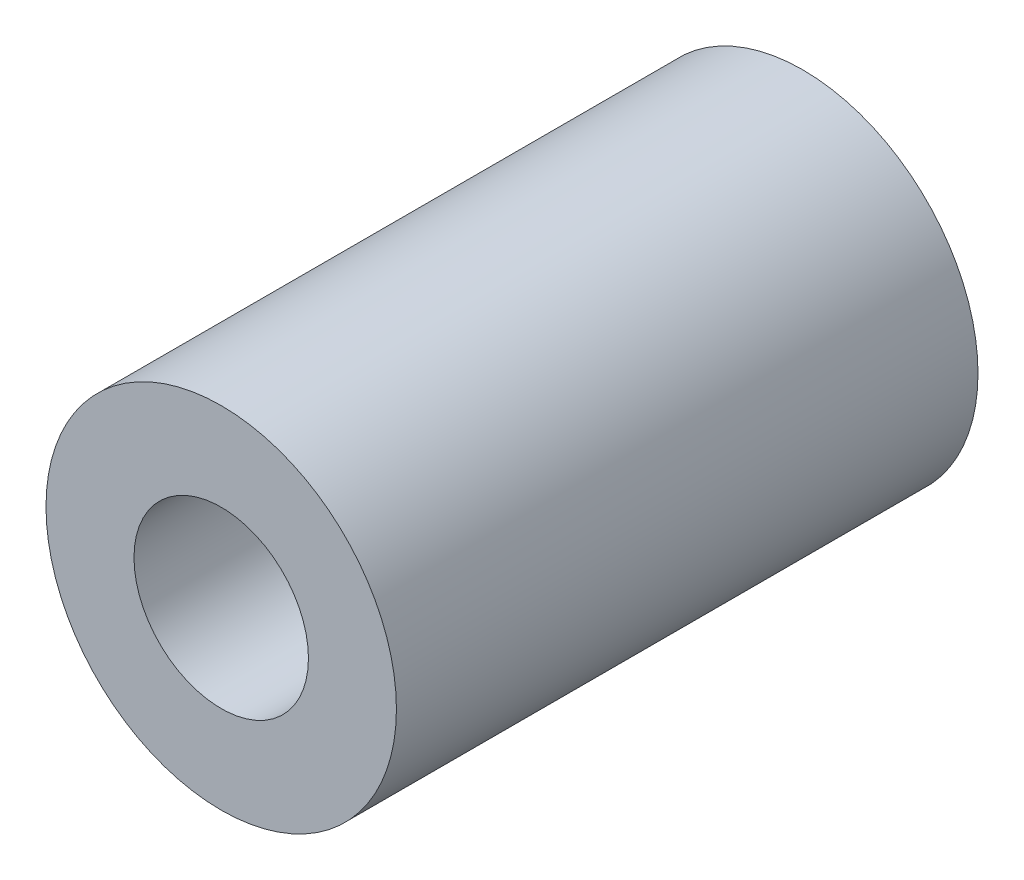
SolidWorks part; units mm, degrees
ref_plane "Front Plane" through (0, 0, 0) normal (0, 0, 1) x (1, 0, 0)
ref_plane "Top Plane" through (0, 0, 0) normal (0, 1, 0) x (1, 0, 0)
ref_plane "Right Plane" through (0, 0, 0) normal (1, 0, 0) x (0, 0, -1)
sketch "Sketch1" plane through (0, 0, 0) normal (0, 0, 1) x (1, 0, 0)
  circle A0 centre (0, 0) radius 6.0255 construction
  circle A1 centre (0, 0) radius 3 construction
  dimension "ID" = 6
  dimension "OD" = 12.051
sketch "Sketch2" plane through (0, 0, 0) normal (1, 0, 0) x (0, 0, -1)
  line L0 (-10, 0) -> (10, 0) construction
  dimension "Length" = 20
sketch "Sketch3" plane through (0, 0, 0) normal (0, 0, 1) x (1, 0, 0)
  circle A0 centre (0, 0) radius 3 construction
  circle A1 centre (0, 0) radius 6.0255 construction
  circle A2 centre (0, 0) radius 3
  circle A3 centre (0, 0) radius 6.0255
extrude "Boss-Extrude1" add sketch "Sketch3" along normal up to vertex (-10 mm away) and the other way up to vertex (-10 mm away) up to point (0, 0, -10) other way up to point (0, 0, 10)
ref_axis "Center Axis 1" through (0, 0, 1.65) along (0, 0, -1)
